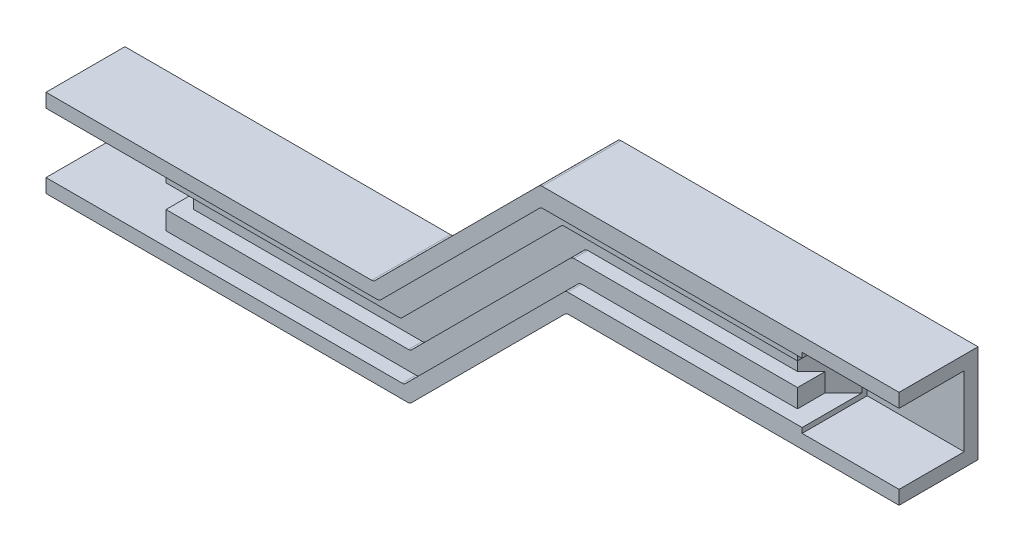
SolidWorks part; units mm, degrees
other "标注1"
sketch "草图9" plane through (0, 16, 0) normal (-0.9711, 0.0526, -0.2329) x (-0.2309, 0.0406, 0.9721)
ref_plane "前视基准面" through (0, 0, 0) normal (0, 0, 1) x (1, 0, 0)
ref_plane "上视基准面" through (0, 0, 0) normal (0, 1, 0) x (1, 0, 0)
ref_plane "右视基准面" through (0, 0, 0) normal (1, 0, 0) x (0, 0, -1)
sketch "草图10" plane through (0, 0, 0) normal (0, 0, 1) x (1, 0, 0)
  line L0 (-92.4, -8) -> (-21.435, -8)
  line L1 (-21.435, -8) -> (13.565, 27)
  line L2 (13.565, 27) -> (92.4, 27)
  line L3 (92.4, 27) -> (92.4, 8)
  line L4 (92.4, 8) -> (21.435, 8)
  line L5 (21.435, 8) -> (-13.565, -27)
  line L6 (-13.565, -27) -> (-92.4, -27)
  line L7 (-92.4, -27) -> (-92.4, -8)
  line L8 (-21.435, -8) -> (21.435, 8) construction
  line L9 (-13.565, -27) -> (13.565, 27) construction
  circle A0 centre (-82.4, -17.5) radius 1.65
  circle A1 centre (82.4, 17.5) radius 1.65
  dimension "D6" = 3.3
  dimension "D1" = 19
  dimension "D2" = 135
  dimension "D3" = 19
  dimension "D4" = 164.8
  dimension "D5" = 35
  dimension "D7" = 10
  dimension "D8" = 10
  dimension "D9" = 9.5
  dimension "D10" = 9.5
extrude "凸台-拉伸1" add sketch "草图10" along normal blind 3
sketch "草图11" plane through (0, 0, 0) normal (0, 0, 1) x (1, 0, 0)
  line L0 (-73.4, -8) -> (-73.4, -27)
  line L1 (-21.435, -8) -> (-92.4, -8) construction
  line L2 (-92.4, -27) -> (-13.565, -27) construction
  line L3 (-73.4, -8) -> (-21.435, -8)
  line L4 (-21.435, -8) -> (13.565, 27)
  line L5 (13.565, 27) -> (71.4, 27)
  line L7 (92.4, 27) -> (13.565, 27) construction
  line L8 (71.4, 27) -> (71.4, 8)
  line L9 (21.435, 8) -> (92.4, 8) construction
  line L10 (71.4, 8) -> (21.435, 8)
  line L11 (21.435, 8) -> (-13.565, -27)
  line L12 (-13.565, -27) -> (-73.4, -27)
  line L13 (-92.4, -8) -> (-92.4, -27) construction
  line L14 (92.4, 8) -> (92.4, 27) construction
  dimension "D1" = 19
  dimension "D2" = 21
extrude "凸台-拉伸2" add sketch "草图11" along normal blind 7 from surface at 3 starting at face at (0, 0, 3)
sketch "草图12" plane through (0, 0, 0) normal (0, 0, 1) x (1, 0, 0)
  line L0 (-92.4, -8) -> (-21.435, -8)
  line L1 (-21.435, -8) -> (-73.4, -8) construction
  line L2 (-21.435, -8) -> (13.565, 27)
  line L3 (13.565, 27) -> (92.4, 27)
  line L4 (92.4, 27) -> (92.4, 24)
  line L5 (92.4, 8) -> (92.4, 27) construction
  line L6 (92.4, 24) -> (14.8076, 24)
  line L7 (14.8076, 24) -> (-20.1924, -11)
  line L8 (-20.1924, -11) -> (-92.4, -11)
  line L9 (-92.4, -8) -> (-92.4, -27) construction
  line L10 (-92.4, -11) -> (-92.4, -8)
  line L11 (-92.4, -24) -> (-92.4, -27)
  line L12 (-92.4, -27) -> (-13.565, -27)
  line L13 (-13.565, -27) -> (21.435, 8)
  line L14 (21.435, 8) -> (92.4, 8)
  line L15 (71.4, 8) -> (92.4, 8) construction
  line L16 (92.4, 11) -> (20.1924, 11)
  line L17 (-92.4, -24) -> (-14.8076, -24)
  line L18 (-14.8076, -24) -> (20.1924, 11)
  line L19 (13.565, 27) -> (-21.435, -8) construction
  line L20 (92.4, 11) -> (92.4, 8)
  dimension "D1" = 3
  dimension "D2" = 3
extrude "凸台-拉伸3" add sketch "草图12" along normal blind 13 from surface at 3 starting at face at (-80.75, -17.5, 3)
chamfer "倒角1" distance 7 angle 45 2 edges at (71.4, 17.5, 10) (-73.4, -17.5, 10)
sketch "草图15" plane through (0, 0, 3) normal (0, 0, 1) x (1, 0, 0)
  line L0 (-69.4, -11) -> (-69.4, -15)
  line L1 (-92.4, -11) -> (-20.1924, -11) construction
  line L2 (-69.4, -15) -> (-18.5355, -15)
  line L3 (-18.5355, -15) -> (16.4645, 20)
  line L4 (16.4645, 20) -> (67.4, 20)
  line L5 (67.4, 20) -> (67.4, 24)
  line L6 (14.8076, 24) -> (92.4, 24) construction
  line L7 (67.4, 24) -> (14.8076, 24)
  line L8 (14.8076, 24) -> (-20.1924, -11)
  line L9 (-20.1924, -11) -> (-69.4, -11)
  line L10 (-69.4, -20) -> (-69.4, -24)
  line L11 (-66.4, -24) -> (-73.4, -24) construction
  line L12 (-69.4, -24) -> (-14.8076, -24)
  line L13 (-14.8076, -24) -> (20.1924, 11)
  line L14 (20.1924, 11) -> (67.4, 11)
  line L15 (92.4, 11) -> (20.1924, 11) construction
  line L16 (67.4, 11) -> (67.4, 15)
  line L17 (67.4, 15) -> (18.5355, 15)
  line L18 (18.5355, 15) -> (-16.4645, -20)
  line L19 (-16.4645, -20) -> (-69.4, -20)
  line L20 (-73.4, -11) -> (-73.4, -24) construction
  line L21 (71.4, 11) -> (71.4, 24) construction
  dimension "D1" = 4
  dimension "D2" = 4
  dimension "D3" = 4
  dimension "D4" = 4
  dimension "D5" = 4
extrude "凸台-拉伸5" add sketch "草图15" along normal blind 10
sketch "草图16" plane through (0, 0, 0) normal (0, 0, 1) x (1, 0, 0)
  line L0 (-92.4, -8) -> (-92.4, -27)
  line L1 (-92.4, -27) -> (-13.565, -27)
  line L2 (-13.565, -27) -> (20.335, 6.9)
  line L3 (20.335, 6.9) -> (92.4, 6.9)
  line L4 (92.4, 6.9) -> (92.4, 28.1)
  line L5 (92.4, 28.1) -> (14.665, 28.1)
  line L6 (14.665, 28.1) -> (-21.435, -8)
  line L7 (-21.435, -8) -> (-92.4, -8)
  line L8 (13.565, 27) -> (-21.435, -8) construction
  line L9 (-13.565, -27) -> (21.435, 8) construction
  line L11 (-21.435, -8) -> (-92.4, -8) construction
  line L12 (-92.4, -27) -> (-13.565, -27) construction
  line L13 (92.4, 27) -> (13.565, 27) construction
  line L14 (92.4, 11) -> (92.4, 24) construction
  circle A0 centre (-82.4, -17.5) radius 1.65
  circle A1 centre (82.4, 17.5) radius 1.65
  dimension "D3" = 3.3
  dimension "D1" = 21.2
  dimension "D2" = 1.1
extrude "凸台-拉伸6" add sketch "草图16" along normal blind 4.1 from offset 1.1 offset against normal yes
sketch "草图17" plane through (0, 0, 0) normal (0, 0, 1) x (1, 0, 0)
  line L12 (92.4, 28.1) -> (92.4, 24)
  line L13 (92.4, 24) -> (14.8076, 24)
  line L14 (14.8076, 24) -> (12.6863, 26.1213)
  line L15 (13.565, 27) -> (-21.435, -8) construction
  line L16 (12.6863, 26.1213) -> (14.665, 28.1)
  line L17 (14.665, 28.1) -> (92.4, 28.1)
  line L18 (92.4, 6.9) -> (20.335, 6.9)
  line L19 (-13.565, -27) -> (21.435, 8) construction
  line L20 (20.335, 6.9) -> (92.4, 6.9) construction
  line L21 (20.335, 6.9) -> (18.2137, 9.0213)
  line L22 (-14.8076, -24) -> (20.1924, 11) construction
  line L23 (18.2137, 9.0213) -> (20.1924, 11)
  line L24 (20.1924, 11) -> (92.4, 11)
  line L25 (92.4, 11) -> (20.1924, 11) construction
  line L26 (92.4, 11) -> (92.4, 6.9)
extrude "凸台-拉伸7" add sketch "草图17" along normal blind 16
sketch "草图18" plane through (0, 0, 16) normal (0, 0, 1) x (1, 0, 0)
  line L7 (92.4, 6.9) -> (92.4, 11) construction
  line L8 (71.4, 25.1) -> (92.4, 25.1)
  line L9 (71.4, 25.1) -> (71.4, 9.9)
  line L10 (71.4, 9.9) -> (92.4, 9.9)
  line L11 (92.4, 25.1) -> (92.4, 9.9)
  line L12 (92.4, 28.1) -> (14.665, 28.1) construction
  line L13 (20.335, 6.9) -> (92.4, 6.9) construction
  dimension "D1" = 3
  dimension "D2" = 3
  dimension "D3" = 21
extrude "切除-拉伸1" cut sketch "草图18" against normal blind 14.1
fillet "圆角1" radius 1 12 edges at (-14.8076, -24, 14.5) (-16.4645, -20, 11.5) (18.5355, 15, 11.5) (20.1924, 11, 14.5) (16.4645, 20, 11.5) (14.8076, 24, 14.5) (-18.5355, -15, 11.5) (-20.1924, -11, 14.5) (-21.435, -8, 7.45) (-13.565, -27, 7.45) (14.665, 28.1, 7.45) (20.335, 6.9, 7.45)
